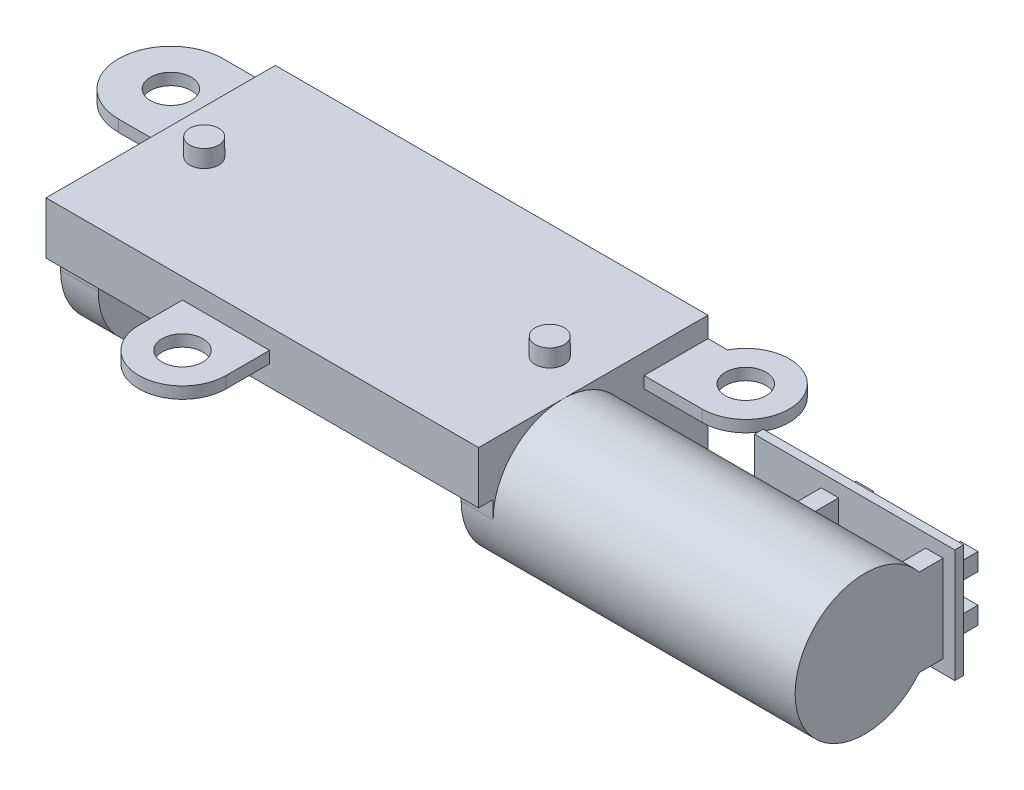
SolidWorks part; units mm, degrees
ref_plane "前视基准面" through (0, 0, 0) normal (0, 0, 1) x (1, 0, 0)
ref_plane "上视基准面" through (0, 0, 0) normal (0, 1, 0) x (1, 0, 0)
ref_plane "右视基准面" through (0, 0, 0) normal (1, 0, 0) x (0, 0, -1)
other "Configuration Table"
sketch "草图1" plane through (0, 0, 0) normal (1, 0, 0) x (0, 0, -1)
  line L9 (-2.4, 2) -> (5, 2)
  line L10 (-2.4, 2) -> (-2.4, -2.4)
  line L11 (-2.4, -2.4) -> (5, -2.4)
  line L12 (5, 2) -> (5, -2.4)
  line L13 (-2.4, 2) -> (-2.9, 2)
  line L14 (-2.4, 2) -> (-2.4, -2.4)
  line L15 (-2.4, -2.4) -> (-2.9, -2.4)
  line L16 (-2.9, 2) -> (-2.9, -2.4)
  line L17 (-2.9, -0.6) -> (5, -0.6)
  line L18 (-2.9, -0.6) -> (-2.9, -2.4)
  line L19 (-2.9, -2.4) -> (5, -2.4)
  line L20 (5, -0.6) -> (5, -2.4)
  circle A0 centre (0, 0) radius 2.4
  dimension "D1" = 4.8
  dimension "D2" = 7.4
  dimension "D3" = 4.4
  dimension "D4" = 7.9
  dimension "D5" = 1.8
extrude "凸台-拉伸1" add sketch "草图1" along normal blind 11.5 contours A0
extrude "凸台-拉伸3" add sketch "草图1<7>" along normal blind 1.1 contours A0 L19 L12 L17 | A0 L17 L14 L11 | L17 L16 L15 L14 | A0 L17 L12 L9 | A0 L14 L17 region at (0, -0.4505, 2.3772) region at (0, 0.7685, -3.5596) region at (0, -1.8814, 1.8576) region at (0, -1.5, 2.65) region at (0, -1.5789, -3.3188)
sketch "草图1<7>" plane through (0, 0, 0) normal (1, 0, 0) x (0, 0, -1) same geometry as "草图1"
extrude "凸台-拉伸4" add sketch "草图1<8>" against normal blind 14.9 from surface contours A0 L19 L12 L17 | L17 A0 | A0 L17 L14 L11 | L17 L16 L15 L14 region at (0, -1.8814, 1.8576) region at (0, -1.5, 2.65) region at (0, -1.3497, 0) region at (0, -1.5789, -3.3188) starting at face at (1.1, -0.3232, -3.2403)
sketch "草图1<8>" plane through (0, 0, 0) normal (1, 0, 0) x (0, 0, -1) same geometry as "草图1"
extrude "凸台-拉伸5" add sketch "草图1<9>" along normal blind 1.3 from surface contours A0 L17 L12 L9 | L9 A0 L17 | A0 L14 L17 region at (0, 0.6092, 0) region at (0, -0.4505, 2.3772) region at (0, 0.7685, -3.5596) starting at face at (-13.8, -1.5, -1.05)
sketch "草图1<9>" plane through (0, 0, 0) normal (1, 0, 0) x (0, 0, -1) same geometry as "草图1"
sketch "草图3" plane through (0, 0, 0) normal (0, 0, 1) x (1, 0, 0)
  line L0 (10.9, 0) -> (11.5, 0) construction
  line L1 (10.9, 1.5) -> (11.5, 1.5)
  line L2 (10.9, 1.5) -> (10.9, -1.5)
  line L3 (10.9, -1.5) -> (11.5, -1.5)
  line L4 (11.5, 1.5) -> (11.5, -1.5)
  line L5 (11.5, -2.4) -> (11.5, 2.4) construction
  line L7 (10.9, 1.1) -> (11.5, 1.1)
  line L8 (10.9, 1.1) -> (10.9, 0.5)
  line L9 (10.9, 0.5) -> (11.5, 0.5)
  line L10 (11.5, 1.1) -> (11.5, 0.5)
  line L11 (10.9, -1.1) -> (11.5, -1.1)
  line L12 (10.9, -1.1) -> (10.9, -0.5)
  line L13 (10.9, -0.5) -> (11.5, -0.5)
  line L14 (11.5, -1.1) -> (11.5, -0.5)
  line L15 (7.3, 1.5) -> (7.9, 1.5)
  line L16 (7.3, 1.5) -> (7.3, -1.5)
  line L17 (7.3, -1.5) -> (7.9, -1.5)
  line L18 (7.9, 1.5) -> (7.9, -1.5)
  line L19 (7.3, 1.1) -> (7.9, 1.1)
  line L20 (7.3, 1.1) -> (7.3, 0.5)
  line L21 (7.3, 0.5) -> (7.9, 0.5)
  line L22 (7.9, 1.1) -> (7.9, 0.5)
  line L23 (7.3, -0.5) -> (7.9, -0.5)
  line L24 (7.3, -0.5) -> (7.3, -1.1)
  line L25 (7.3, -1.1) -> (7.9, -1.1)
  line L26 (7.9, -0.5) -> (7.9, -1.1)
  dimension "D1" = 3
  dimension "D2" = 0.6
  dimension "D3" = 0.4
  dimension "D4" = 0.4
  dimension "D5" = 0.6
  dimension "D6" = 0.6
  dimension "D7" = 3
extrude "凸台-拉伸6" add sketch "草图3" against normal blind 3.9 contours L2 L9 L4 L7 | L13 L2 L11 L4 | L16 L21 L18 L19 | L16 L25 L18 L23 | L20 L19 L22 L21 region at (11.2, 0.8, 0) region at (11.2, -0.8, 0) region at (7.6, 0.8, 0) region at (7.6, -0.8, 0)
extrude "凸台-拉伸7" add sketch "草图3<3>" against normal blind 3 contours L2 L3 L4 L1 | L18 L17 L16 L15
sketch "草图3<3>" plane through (0, 0, 0) normal (0, 0, 1) x (1, 0, 0) same geometry as "草图3"
sketch "草图4" plane through (0, 0, 0) normal (0, 0, 1) x (1, 0, 0)
  line L0 (11.9, 0) -> (5, 0) construction
  line L1 (11.9, 1.95) -> (5, 1.95)
  line L2 (11.9, 1.95) -> (11.9, -1.95)
  line L3 (11.9, -1.95) -> (5, -1.95)
  line L4 (5, 1.95) -> (5, -1.95)
  line L5 (11.5, 1.1) -> (11.5, 0.5) construction
  dimension "D1" = 3.9
  dimension "D2" = 6.9
  dimension "D3" = 0.4
extrude "凸台-拉伸8" add sketch "草图4" along normal blind 0.3 from surface contours L1 L4 L3 L2 starting at face at (11.2, 1.3, -3)
sketch "草图6" plane through (0, -0.6, 0) normal (0, 1, 0) x (1, 0, 0)
  line L0 (0, 5) -> (0, -2.4) construction
  line L1 (-12.5, 5) -> (0, 5)
  line L2 (-12.5, 5) -> (-12.5, -2.5)
  line L3 (-12.5, -2.5) -> (0, -2.5)
  line L4 (0, 5) -> (0, -2.5)
  line L5 (-12.5, 5) -> (-12.5, -2.4) construction
  line L6 (1.1, -2.9) -> (-13.8, -2.9) construction
  line L7 (-12.5, 5) -> (0, 5) construction
  dimension "D1" = 0.4
extrude "切除-拉伸1" cut sketch "草图6" against normal offset from surface (0.7 mm away) 1.1 up to face at (-4.86, -2.4, -0.84)
sketch "草图5" plane through (0, 0, 0) normal (0, 1, 0) x (1, 0, 0)
  line L0 (1.1, 1.3266) -> (1.1, 5) construction
  line L1 (3.1, 5) -> (1.1, 5)
  line L2 (3.1, 5) -> (3.1, 2.8)
  line L3 (3.1, 2.8) -> (1.1, 2.8)
  line L4 (1.1, 5) -> (1.1, 2.8)
  line L6 (4.6, 8.9261) -> (4.6, 7.1067)
  line L8 (0, 1.3266) -> (0, 5) construction
  line L9 (-14.0082, -5.9) -> (-9.9239, -5.9)
  line L12 (-9.1, -4.4) -> (-6.1, -4.4)
  line L13 (-9.1, -4.4) -> (-9.1, -2.9)
  line L14 (-9.1, -2.9) -> (-6.1, -2.9)
  line L15 (-6.1, -4.4) -> (-6.1, -2.9)
  line L16 (-13.8, 5) -> (-13.8, -1.3266) construction
  line L17 (-12.5, 5) -> (0, 5) construction
  line L18 (1.1, -2.9) -> (-13.8, -2.9) construction
  line L20 (-15.6, 5) -> (-13.8, 5)
  line L21 (-15.6, 5) -> (-15.6, 1.4)
  line L22 (-15.6, 1.4) -> (-13.8, 1.4)
  line L23 (-13.8, 5) -> (-13.8, 1.4)
  circle A0 centre (3.1, 4.3) radius 1.5
  circle A1 centre (3.1, 4.3) radius 0.7
  circle A2 centre (-7.6, -4.4) radius 1.5
  circle A3 centre (-7.6, -4.4) radius 0.7
  circle A4 centre (-15.6, 3.2) radius 1.8
  circle A5 centre (-15.6, 3.2) radius 0.7
  dimension "D1" = 0.8
  dimension "D2" = 3
  dimension "D7" = 3.6
  dimension "D3" = 2.2
  dimension "D4" = 4.6
  dimension "D5" = 10.9
  dimension "D6" = 7.7
extrude "凸台-拉伸9" add sketch "草图5" against normal blind 0.4 from surface contours A0 L1 L4 L3 | A2 L13 L14 | A2 L14 L15 | A4 L22 L23 | A4 L23 L20 | A0 | A1 | A2 | A3 | A4 | A5 region at (1.5315, 0, -3.6949) region at (-6.4351, 0, 3.2351) region at (-8.7649, 0, 3.2351) region at (-14.2021, 0, -4.5979) region at (-14.2021, 0, -1.8021) starting at face at (-6.25, -1.3, -1.25)
sketch "草图7" plane through (0, 0, 0) normal (-1, 0, 0) x (0, 0, 1)
  line L1 (-2.5, 3.6598) -> (-0.9, 3.6598)
  line L2 (-2.5, 3.6598) -> (-2.5, 3.3325)
  line L3 (-2.5, 3.3325) -> (-0.9, 3.3325)
  line L4 (-0.9, 3.6598) -> (-0.9, 3.3325)
  circle A0 centre (0, 0) radius 0.9
  circle A1 centre (-3.3, 0) radius 0.8
  dimension "D1" = 1.8
  dimension "D2" = 1.6
  dimension "D3" = 1.6
  dimension "D4" = 3.3
extrude "凸台-拉伸10" add sketch "草图7" along normal up to surface (12.5 mm away) contours A1 | A0 up to face at (-12.5, 0.0478, 0.1969)
sketch "草图8" plane through (0, -2.4, 0) normal (0, -1, 0) x (1, 0, 0)
  line L0 (-12.8, 6.0889) -> (-12.8, 3.0212)
  line L1 (-12.8, 3.0212) -> (0.1, 3.0212)
  line L2 (0.1, 3.0212) -> (0.1, 5.2574)
  line L3 (-13.8, -1.05) -> (1.1, -1.05)
  line L4 (-13.8, -5) -> (-13.8, 2.9) construction
  line L5 (1.1, 0) -> (1.1, -5) construction
  circle A0 centre (-12.3, -1.05) radius 0.5
  circle A1 centre (-0.4, -1.05) radius 0.5
  dimension "D1" = 1
  dimension "D2" = 12.9
  dimension "D3" = 1
extrude "凸台-拉伸11" add sketch "草图8" along normal blind 0.6 contours A0 | A1
ref_plane "基准面1" through (0, -10, 0) normal (0, 1, 0) x (1, 0, 0)
mirror "镜向2" about plane through (0, -10, 0) normal (0, 1, 0) of bodies 131
sketch "草图9" plane through (0, -10, 0) normal (0, 1, 0) x (1, 0, 0)
  line L1 (-26.7141, 18.6732) -> (29.0645, 18.6732)
  line L2 (-26.7141, 18.6732) -> (-26.7141, -17.8633)
  line L3 (-26.7141, -17.8633) -> (29.0645, -17.8633)
  line L4 (29.0645, 18.6732) -> (29.0645, -17.8633)
extrude "切除-拉伸2" cut sketch "草图9" along normal through all
